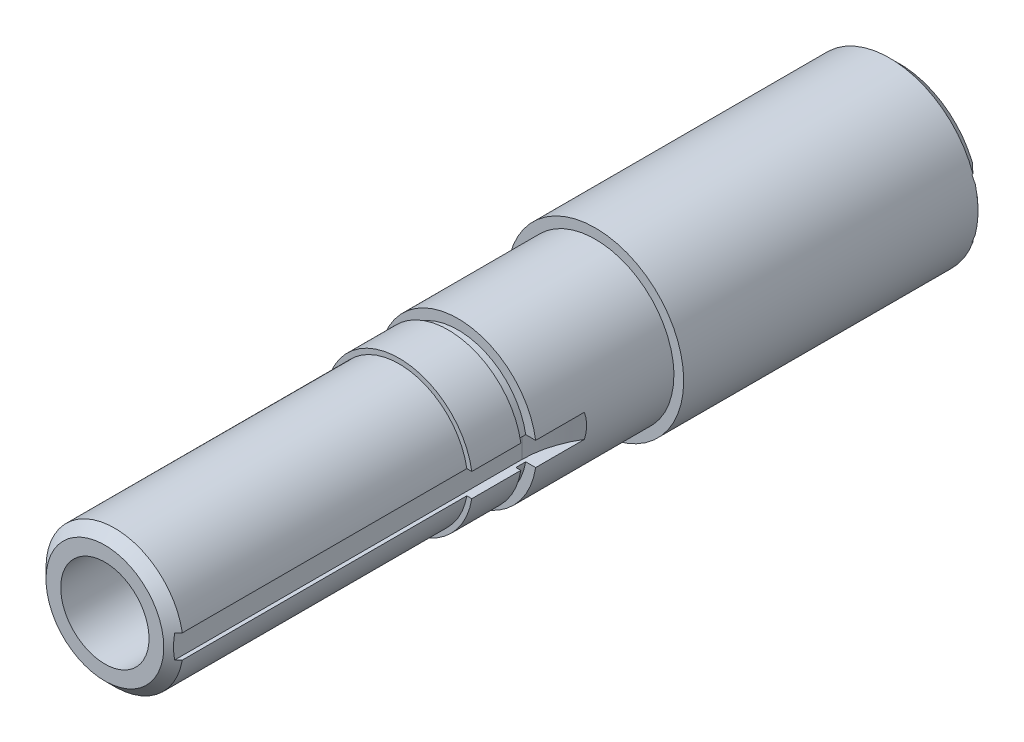
SolidWorks part; units mm, degrees
ref_plane "Plan de face" through (0, 0, 0) normal (0, 0, 1) x (1, 0, 0)
ref_plane "Plan de dessus" through (0, 0, 0) normal (0, 1, 0) x (1, 0, 0)
ref_plane "Plan de droite" through (0, 0, 0) normal (1, 0, 0) x (0, 0, -1)
sketch "Esquisse1" plane through (0, 0, 0) normal (0, 0, 1) x (1, 0, 0)
  circle A0 centre (0, 0) radius 9
  dimension "D1" = 18
extrude "Extrusion1" add sketch "Esquisse1" along normal blind 31
sketch "Esquisse2" plane through (0, 0, 31) normal (0, 0, 1) x (1, 0, 0)
  circle A0 centre (0, 0) radius 8
  circle A1 centre (0, 0) radius 9 construction
  dimension "D1" = 16
extrude "Extrusion2" add sketch "Esquisse2" along normal blind 14
sketch "Esquisse3" plane through (0, 0, 45) normal (0, 0, 1) x (1, 0, 0)
  circle A0 centre (0, 0) radius 7.5
  dimension "D1" = 15
extrude "Extrusion3" add sketch "Esquisse3" along normal blind 6
cosmetic thread "Représentation de filetage3" parameters "D2"=14
cosmetic thread "Représentation de filetage4" parameters "D2"=14
sketch "Esquisse4" plane through (0, 0, 51) normal (0, 0, 1) x (1, 0, 0)
  circle A0 centre (0, 0) radius 7
  dimension "D1" = 14
extrude "Extrusion4" add sketch "Esquisse4" along normal blind 30
chamfer "Chanfrein1" distance 1 angle 45 1 edges at (7, 0, 81)
chamfer "Chanfrein2" distance 1 angle 45 1 edges at (9, 0, 0)
sketch "Esquisse5" plane through (0, 0, 0) normal (0, 0, -1) x (-1, 0, 0)
  circle A0 centre (0, 0) radius 4
  circle A1 centre (0, 0) radius 9 construction
  dimension "D1" = 8
extrude "Enlèv. mat.-Extru.1" cut sketch "Esquisse5" against normal blind 54
sketch "Esquisse6" plane through (0, 0, 54) normal (0, 0, -1) x (-1, 0, 0)
  circle A0 centre (0, 0) radius 3
  dimension "D1" = 6
extrude "Enlèv. mat.-Extru.2" cut sketch "Esquisse6" against normal blind 14
cosmetic thread "Représentation de filetage5" parameters "D2"=8
cosmetic thread "Représentation de filetage6" parameters "D2"=8
chamfer "Chanfrein3" distance 1 angle 45 1 edges at (-3, 0, 54)
sketch "Esquisse7" plane through (0, 0, 81) normal (0, 0, 1) x (1, 0, 0)
  circle A0 centre (0, 0) radius 4.5
  dimension "D1" = 9
extrude "Enlèv. mat.-Extru.3" cut sketch "Esquisse7" against normal blind 13
chamfer "Chanfrein4" distance 1 angle 45 1 edges at (3, 0, 68)
sketch "Esquisse8" plane through (0, 0, 0) normal (0, 1, 0) x (1, 0, 0)
  line L0 (6.5, -81) -> (9.2738, -81)
  line L2 (6.5, -81) -> (6.5, -45)
  line L4 (-7.5, -45) -> (7.5, -45) construction
  line L5 (8, -45) -> (8, -31) construction
  line L6 (7, -80) -> (7, -51) construction
  line L7 (9.2738, -81) -> (9.2738, -39.8887)
  line L8 (9.2738, -39.8887) -> (8, -39.8887)
  arc A0 (6.5, -45) -> (8, -39.8887) centre (15.9585, -45) cw
  dimension "D1" = 0.5
  dimension "D2" = 0.5
extrude "Enlèv. mat.-Extru.4" cut sketch "Esquisse8" against normal blind 1.2 and the other way blind 1.2
sketch "Esquisse9" plane through (0, 0, 0) normal (0, 1, 0) x (1, 0, 0)
  line L0 (8, 0) -> (-8, 0) construction
  line L1 (9, -31) -> (9, -1) construction
  circle A0 centre (0, 17) radius 20
  dimension "D1" = 40
  dimension "D2" = 17
  dimension "D3" = 9
extrude "Enlèv. mat.-Extru.5" cut sketch "Esquisse9" against normal blind 3 and the other way blind 3
sketch "Esquisse10" plane through (0, 0, 45) normal (0, 0, 1) x (1, 0, 0)
  circle A0 centre (0, 0) radius 7.5
  circle A1 centre (0, 0) radius 7.0004
  arc A2 (7.4034, 1.2) -> (7.4034, -1.2) centre (0, 0) ccw construction
  dimension "D1" = 14.0008
extrude "Enlèv. mat.-Extru.6" cut sketch "Esquisse10" along normal blind 1
